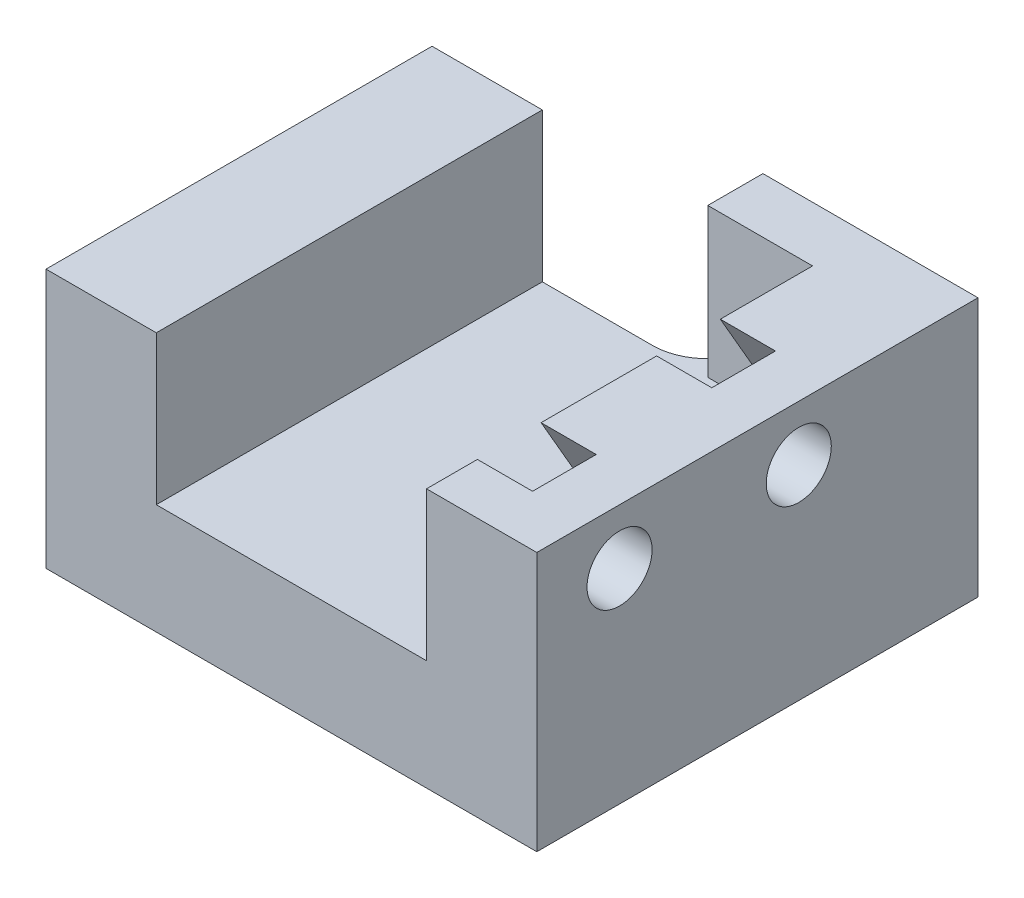
SolidWorks part; units mm, degrees
ref_plane "Front Plane" through (0, 0, 0) normal (0, 0, 1) x (1, 0, 0)
ref_plane "Top Plane" through (0, 0, 0) normal (0, 1, 0) x (1, 0, 0)
ref_plane "Right Plane" through (0, 0, 0) normal (1, 0, 0) x (0, 0, -1)
sketch "Sketch1" plane through (0, 0, 0) normal (0, 1, 0) x (1, 0, 0)
  line L0 (2.075, -3.5) -> (2.825, -3.5)
  line L1 (2.075, -3.5) -> (-2.075, -3.5)
  line L2 (2.075, -3.5) -> (2.075, 3.5) construction
  line L3 (2.075, 3.5) -> (-2.075, 3.5)
  line L4 (-2.075, -3.5) -> (-2.075, 3.5) construction
  line L5 (2.075, -3.5) -> (-2.075, 3.5) construction
  line L6 (2.075, 3.5) -> (-2.075, -3.5) construction
  line L7 (2.825, -3.5) -> (3.825, -3.5)
  line L9 (3.825, 3.5) -> (2.825, 3.5)
  line L10 (2.825, 3.5) -> (2.075, 3.5)
  line L11 (3.825, 3.5) -> (4.825, 3.5)
  line L12 (4.825, 3.5) -> (4.825, -3.5)
  line L13 (4.825, -3.5) -> (3.825, -3.5)
  line L14 (-2.075, 3.5) -> (-4.075, 3.5)
  line L15 (-4.075, 3.5) -> (-4.075, -3.5)
  line L16 (-4.075, -3.5) -> (-2.075, -3.5)
  line L17 (3.825, 3.5) -> (3.825, -3.5) construction
  point P0 (0, 0)
  point P7 (0, 0)
  dimension "D1" = 4.15
  dimension "D2" = 7
  dimension "D3" = 0.75
  dimension "D4" = 1
  dimension "D5" = 1
  dimension "D6" = 2
extrude "Boss-Extrude1" add sketch "Sketch1" along normal blind 2
sketch "Sketch2" plane through (0, 2, 0) normal (0, 1, 0) x (1, 0, 0)
  line L1 (-4.075, 3.5) -> (-2.075, 3.5)
  line L2 (-4.075, 3.5) -> (-4.075, -3.5)
  line L3 (-4.075, -3.5) -> (-2.075, -3.5)
  line L4 (-2.075, 3.5) -> (-2.075, -3.5)
  line L5 (2.825, 3.5) -> (4.825, 3.5)
  line L6 (2.825, 3.5) -> (2.825, -3.5)
  line L7 (2.825, -3.5) -> (4.825, -3.5)
  line L8 (4.825, 3.5) -> (4.825, -3.5)
extrude "Boss-Extrude2" add sketch "Sketch2" along normal blind 2.7
sketch "Sketch3" plane through (2.825, 0, 0) normal (-1, 0, 0) x (0, 0, 1)
  line L0 (-3.5, 4.7) -> (3.5, 4.7) construction
  line L1 (-0.0953, 3.7) -> (-0.6726, 4.7)
  line L2 (-0.6726, 4.7) -> (-1.8274, 4.7)
  line L3 (-1.8274, 4.7) -> (-2.4047, 3.7)
  line L4 (-2.4047, 3.7) -> (-1.8274, 2.7)
  line L5 (-1.8274, 2.7) -> (-0.6726, 2.7)
  line L6 (-0.6726, 2.7) -> (-0.0953, 3.7)
  line L7 (3.1547, 3.7) -> (2.5774, 4.7)
  line L8 (2.5774, 4.7) -> (1.4226, 4.7)
  line L9 (1.4226, 4.7) -> (0.8453, 3.7)
  line L10 (0.8453, 3.7) -> (1.4226, 2.7)
  line L11 (1.4226, 2.7) -> (2.5774, 2.7)
  line L12 (2.5774, 2.7) -> (3.1547, 3.7)
  line L13 (-3.5, 4.7) -> (-3.5, 2) construction
  line L15 (-3.5, 4.7) -> (-3.5, 0) construction
  circle A0 centre (-1.25, 3.7) radius 1 construction
  circle A1 centre (2, 3.7) radius 1 construction
  point P9 (0, 0)
  point P17 (1.8577, 3.35)
  dimension "D1" = 2
  dimension "D2" = 2.25
  dimension "D3" = 5.5
extrude "Cut-Extrude1" cut sketch "Sketch3" against normal blind 1
sketch "Sketch4" plane through (4.825, 0, 0) normal (1, 0, 0) x (0, 0, -1)
  circle A0 centre (-2, 3.7) radius 0.59
  circle A1 centre (1.25, 3.7) radius 0.59
  dimension "D1" = 1.18
extrude "Cut-Extrude2" cut sketch "Sketch4" against normal up to next
sketch "Sketch5" plane through (0, 0, -3.5) normal (0, 0, -1) x (-1, 0, 0)
  line L0 (-2.075, 0) -> (2.075, 0) construction
  line L1 (-4.825, 4.7) -> (-0.925, 4.7)
  line L2 (-4.825, 4.7) -> (-4.825, 0)
  line L3 (-4.825, 0) -> (-0.925, 0)
  line L4 (-0.925, 4.7) -> (-0.925, 0)
  line L5 (2.075, 4.7) -> (2.075, 2) construction
  dimension "D1" = 3
extrude "Boss-Extrude3" add sketch "Sketch5" along normal blind 1
fillet "Fillet1" radius 1 1 edges at (0.925, 1, -3.5)
equation "\"Clearance\"=0.75"
equation "\"D3@Sketch1\"=\"Clearance\""
equation "\"NutThickness\"=1"
equation "\"D4@Sketch1\"=\"NutThickness\""
equation "\"LargerWallThickness\"=2"
equation "\"D6@Sketch1\"=\"LargerWallThickness\""
equation "\"D1@Boss-Extrude1\"=\"LargerWallThickness\""
